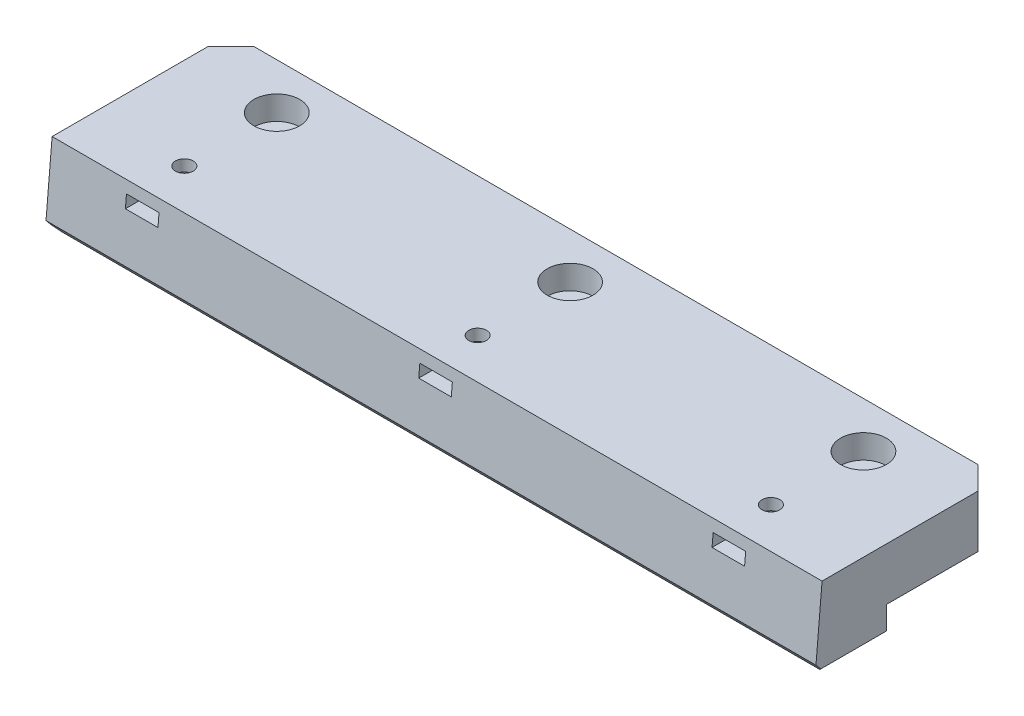
SolidWorks part; units mm, degrees
material "PET"
ref_plane "Front Plane" through (0, 0, 0) normal (0, 0, 1) x (1, 0, 0)
ref_plane "Top Plane" through (0, 0, 0) normal (0, 1, 0) x (1, 0, 0)
ref_plane "Right Plane" through (0, 0, 0) normal (1, 0, 0) x (0, 0, -1)
sketch "Sketch1" plane through (0, 0, 0) normal (1, 0, 0) x (0, 0, -1)
  line L1 (12.7, -4.7625) -> (-12.7, -4.7625)
  line L2 (12.7, -4.7625) -> (12.7, 4.7625)
  line L3 (12.7, 4.7625) -> (-12.7, 4.7625)
  line L4 (-12.7, -4.7625) -> (-12.7, 4.7625)
  line L5 (12.7, -4.7625) -> (-12.7, 4.7625) construction
  line L6 (12.7, 4.7625) -> (-12.7, -4.7625) construction
  point P0 (0, 0)
  dimension "D1" = 9.525
  dimension "D2" = 25.4
extrude "Boss-Extrude1" add sketch "Sketch1" along normal mid plane 213.36
sketch "Sketch2" plane through (-106.68, 0, 0) normal (-1, 0, 0) x (0, 0, 1)
  line L0 (12.7, 4.7625) -> (37.438, 4.7625)
  line L1 (12.7, 4.7625) -> (12.7, -4.7625) construction
  line L2 (37.438, 4.7625) -> (38.829, -11.1363)
  line L4 (38.829, -11.1363) -> (12.7, -11.1363)
  line L9 (12.7, -11.1363) -> (12.7, 4.7625)
  line L10 (-12.7, 4.7625) -> (12.7, 4.7625) construction
  line L11 (25.5674, 149.1875) -> (39.494, -9.9944) construction
  line L12 (19.05, -11.1363) -> (38.1, -11.1363) construction
  dimension "D1" = 0.762
extrude "Boss-Extrude2" add sketch "Sketch2" against normal through all
chamfer "Chamfer1" distance 6.35 angle 45 4 edges at (106.68, -7.9494, 12.7) (106.68, 0, -12.7) (-106.68, 0, -12.7) (-106.68, -7.9494, 12.7)
chamfer "Chamfer2" distance 3.175 angle 45 1 edges at (0, -11.1363, 38.829) first distance on face at (0, -3.1869, 38.1335)
hole_wizard "#8 Clearance Hole1" positions "Sketch3" profile "Sketch4" hole size "#8" standard "ANSI Inch" end condition up to next
sketch "Sketch3" plane through (0, -11.1363, 0) normal (0, -1, 0) x (-1, 0, 0)
  line L0 (0, -38.5523) -> (0, -12.7) construction
  line L1 (106.68, -38.5523) -> (-106.68, -38.5523) construction
  line L2 (-100.33, -12.7) -> (100.33, -12.7) construction
  line L3 (0, -12.7) -> (0, 12.7) construction
  line L4 (-100.33, 12.7) -> (100.33, 12.7) construction
  line L6 (0, 0) -> (106.68, 0) construction
  line L7 (106.68, -19.05) -> (106.68, 6.35) construction
  line L9 (0, -25.6261) -> (106.68, -25.6261) construction
  line L10 (106.68, -19.05) -> (106.68, -35.8983) construction
  point P12 (0, 0)
  point P19 (0, -25.6261)
  point P24 (81.28, -25.6261)
  point P26 (81.28, 0)
  point P35 (-81.28, 0)
  point P36 (-81.28, -25.6261)
  dimension "D1" = 25.4
sketch "Sketch4" plane through (81.28, -11.1363, 25.6261) normal (1, 0, 0) x (0, 0, -1)
  line L0 (0, 0) -> (0, 15.8988)
  line L1 (0, 15.8988) -> (2.4574, 15.8988)
  line L2 (2.4574, 15.8988) -> (2.4574, 0)
  line L5 (2.4574, 0) -> (0, 0)
  line L11 (0, -6.35) -> (0, 107.95) construction
  dimension "Thru Hole Dia." = 4.9149
  dimension "Thru Hole Depth" = 15.8988
chamfer "Chamfer3" distance 1.5875 angle 45 10 edges at (-106.68, -4.7625, 6.35) (-103.505, -4.7625, -9.525) (0, -4.7625, -12.7) (103.505, -4.7625, -9.525) (106.68, -4.7625, 6.35) (106.68, -11.1363, 27.4741) (103.505, -11.1363, 15.875) (0, -11.1363, 12.7) (-103.505, -11.1363, 15.875) (-106.68, -11.1363, 27.4741)
sketch "Sketch5" plane through (0, 4.7625, 0) normal (0, 1, 0) x (1, 0, 0)
  line L0 (106.68, 6.35) -> (106.68, -37.438) construction
  line L1 (85.7885, -37.438) -> (85.7885, -23.0232)
  line L2 (85.7885, -23.0232) -> (81.28, -20.4202)
  line L3 (81.28, -20.4202) -> (76.7715, -23.0232)
  line L4 (76.7715, -23.0232) -> (76.7715, -37.438)
  line L20 (73.5965, -37.438) -> (76.7715, -37.438)
  line L21 (73.5965, -37.438) -> (73.5965, -17.2452)
  line L22 (73.5965, -17.2452) -> (88.9635, -17.2452)
  line L23 (88.9635, -37.438) -> (88.9635, -17.2452)
  line L24 (76.7715, -28.2291) -> (81.28, -30.8321) [skipped]
  line L25 (81.28, -30.8321) -> (85.7885, -28.2291) [skipped]
  line L26 (85.7885, -37.438) -> (88.9635, -37.438)
  line L27 (81.28, -20.4202) -> (81.28, -17.2452) construction
  line L28 (4.5085, -37.438) -> (4.5085, -23.0232)
  line L29 (4.5085, -23.0232) -> (0, -20.4202)
  line L30 (0, -20.4202) -> (-4.5085, -23.0232)
  line L31 (-4.5085, -23.0232) -> (-4.5085, -37.438)
  line L32 (-7.6835, -37.438) -> (-4.5085, -37.438)
  line L33 (-7.6835, -37.438) -> (-7.6835, -17.2452)
  line L34 (-7.6835, -17.2452) -> (7.6835, -17.2452)
  line L35 (7.6835, -37.438) -> (7.6835, -17.2452)
  line L36 (4.5085, -37.438) -> (7.6835, -37.438)
  line L37 (0, -20.4202) -> (0, -17.2452) construction
  line L38 (-76.7715, -37.438) -> (-76.7715, -23.0232)
  line L39 (-76.7715, -23.0232) -> (-81.28, -20.4202)
  line L40 (-81.28, -20.4202) -> (-85.7885, -23.0232)
  line L41 (-85.7885, -23.0232) -> (-85.7885, -37.438)
  line L42 (-88.9635, -37.438) -> (-85.7885, -37.438)
  line L43 (-88.9635, -37.438) -> (-88.9635, -17.2452)
  line L44 (-88.9635, -17.2452) -> (-73.5965, -17.2452)
  line L45 (-73.5965, -37.438) -> (-73.5965, -17.2452)
  line L46 (-76.7715, -37.438) -> (-73.5965, -37.438)
  line L47 (-81.28, -20.4202) -> (-81.28, -17.2452) construction
  line L48 (85.7885, -37.438) -> (4.5085, -37.438) construction
  line L49 (106.68, -37.438) -> (-106.68, -37.438) construction
  circle A0 centre (81.28, -25.6261) radius 4.5085 construction
  circle A1 centre (0, -25.6261) radius 4.5085 construction
  circle A2 centre (-81.28, -25.6261) radius 4.5085 construction
  point P7 (0, 0)
  point P48 (0, 0)
  point P49 (0, 0)
  point P52 (65.0017, -33.0851)
  point P53 (65.0017, -33.0851)
  dimension "D1" = 9.017
  dimension "D2" = 3.175
  dimension "D3" = 3
  dimension "D4" = 81.28
  dimension "D5" = 0
extrude "Boss-Extrude3" add sketch "Sketch5" along normal blind 3.429
sketch "Sketch6" plane through (0, 8.1915, 0) normal (0, 1, 0) x (1, 0, 0)
  line L1 (-88.9635, -17.2452) -> (-73.5965, -17.2452)
  line L2 (-88.9635, -17.2452) -> (-88.9635, -37.438)
  line L3 (-88.9635, -37.438) -> (-73.5965, -37.438)
  line L4 (-73.5965, -17.2452) -> (-73.5965, -37.438)
  line L5 (-7.6835, -17.2452) -> (7.6835, -17.2452)
  line L6 (-7.6835, -17.2452) -> (-7.6835, -37.438)
  line L7 (-7.6835, -37.438) -> (7.6835, -37.438)
  line L8 (7.6835, -17.2452) -> (7.6835, -37.438)
  line L9 (73.5965, -17.2452) -> (88.9635, -17.2452)
  line L10 (73.5965, -17.2452) -> (73.5965, -37.438)
  line L11 (73.5965, -37.438) -> (88.9635, -37.438)
  line L12 (88.9635, -17.2452) -> (88.9635, -37.438)
  circle A0 centre (81.28, -25.6261) radius 2.4574 construction
  circle A1 centre (0, -25.6261) radius 2.4574 construction
  circle A2 centre (-81.28, -25.6261) radius 2.4574 construction
  circle A3 centre (81.28, -25.6261) radius 2.4574
  circle A4 centre (0, -25.6261) radius 2.4574
  circle A5 centre (-81.28, -25.6261) radius 2.4574
extrude "Boss-Extrude4" add sketch "Sketch6" along normal blind 3.175
chamfer "Chamfer4" [suppressed] distance 6.604 angle 45
sketch "Sketch7" plane through (0, 4.7625, 0) normal (0, 1, 0) x (1, 0, 0)
  line L44 (-73.5965, -17.2452) -> (-73.5965, -37.438)
  line L45 (-73.5965, -37.438) -> (-7.6835, -37.438)
  line L47 (-7.6835, -37.438) -> (-7.6835, -17.2452)
  line L49 (-7.6835, -17.2452) -> (7.6835, -17.2452)
  line L50 (7.6835, -17.2452) -> (7.6835, -37.438)
  line L51 (7.6835, -37.438) -> (73.5965, -37.438)
  line L52 (73.5965, -37.438) -> (73.5965, -17.2452)
  line L53 (73.5965, -17.2452) -> (88.9635, -17.2452)
  line L54 (88.9635, -17.2452) -> (88.9635, -37.438)
  line L55 (88.9635, -37.438) -> (106.68, -37.438)
  line L56 (106.68, -37.438) -> (106.68, 6.35)
  line L57 (106.68, 6.35) -> (100.33, 12.7)
  line L58 (100.33, 12.7) -> (-100.33, 12.7)
  line L59 (-100.33, 12.7) -> (-106.68, 6.35)
  line L60 (-106.68, 6.35) -> (-106.68, -37.438)
  line L61 (-106.68, -37.438) -> (-88.9635, -37.438)
  line L62 (-88.9635, -37.438) -> (-88.9635, -17.2452)
  line L63 (-88.9635, -17.2452) -> (-73.5965, -17.2452)
  line L64 (-73.5965, -17.2452) -> (-73.5965, -37.438)
  line L65 (-73.5965, -37.438) -> (-7.6835, -37.438)
  line L66 (-7.6835, -37.438) -> (-7.6835, -17.2452)
  line L67 (-7.6835, -17.2452) -> (7.6835, -17.2452)
  line L68 (7.6835, -17.2452) -> (7.6835, -37.438)
  line L69 (7.6835, -37.438) -> (73.5965, -37.438)
  line L70 (73.5965, -37.438) -> (73.5965, -17.2452)
  line L71 (73.5965, -17.2452) -> (88.9635, -17.2452)
  line L72 (88.9635, -17.2452) -> (88.9635, -37.438)
  line L73 (88.9635, -37.438) -> (106.68, -37.438)
  line L74 (106.68, -37.438) -> (106.68, 6.35)
  line L75 (106.68, 6.35) -> (100.33, 12.7)
  line L76 (100.33, 12.7) -> (-100.33, 12.7)
  line L77 (-100.33, 12.7) -> (-106.68, 6.35)
  line L78 (-106.68, 6.35) -> (-106.68, -37.438)
  line L79 (-106.68, -37.438) -> (-88.9635, -37.438)
  line L80 (-88.9635, -37.438) -> (-88.9635, -17.2452)
  line L81 (-88.9635, -17.2452) -> (-73.5965, -17.2452)
  circle A0 centre (81.28, 0) radius 6.35
  circle A1 centre (0, 0) radius 6.35
  circle A2 centre (-81.28, 0) radius 6.35
  point P0 (88.9635, -37.438)
  point P27 (-88.9635, -37.438)
  point P31 (-73.5965, -37.438)
  point P33 (-7.6835, -37.438)
  point P35 (7.6835, -37.438)
  point P37 (88.9635, -37.438)
  point P39 (73.5965, -37.438)
  dimension "D5" = 12.7
  dimension "D1" = 0
extrude "Boss-Extrude5" add sketch "Sketch7" along normal up to surface (6.604 mm away) up to face at (81.28, 11.3665, 27.3416)
sketch "Sketch8" plane through (-106.68, 0, 0) normal (-1, 0, 0) x (0, 0, 1)
  line L0 (37.438, 4.7625) -> (36.8603, 11.3665)
  line L2 (36.8603, 11.3665) -> (37.438, 11.3665)
  line L3 (37.438, 11.3665) -> (37.438, 4.7625)
  line L4 (38.5523, -7.9734) -> (37.438, 4.7625) construction
  line L5 (-6.35, 11.3665) -> (37.438, 11.3665) construction
  point P3 (0, 0)
extrude "Cut-Extrude1" cut sketch "Sketch8" against normal through all
